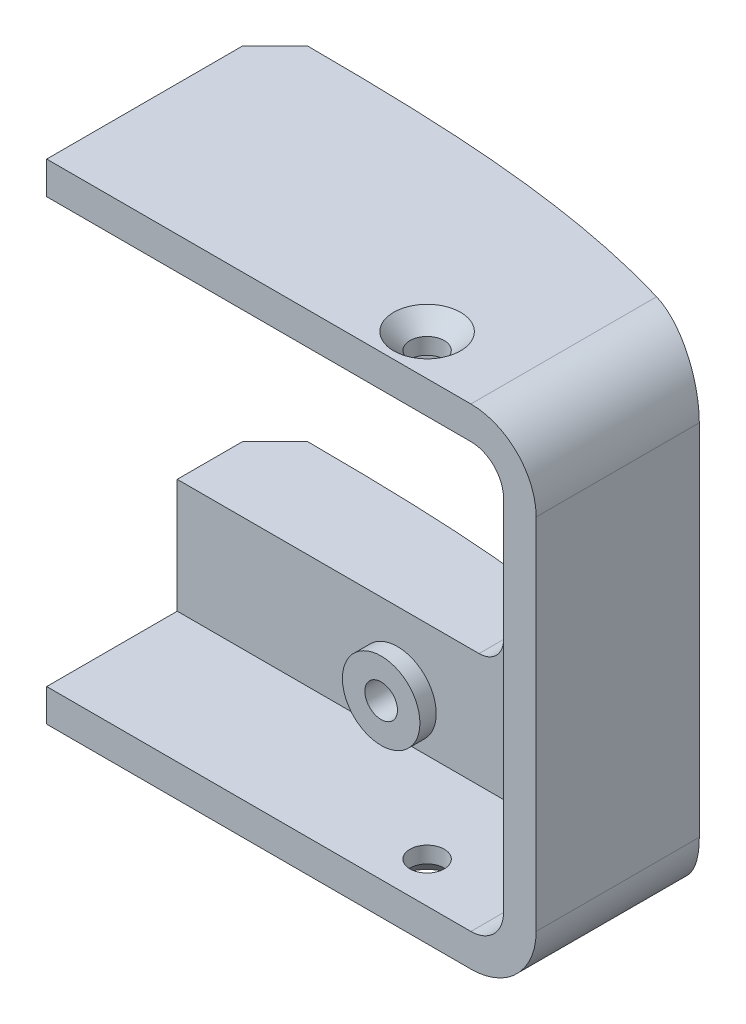
SolidWorks part; units mm, degrees
ref_plane "前视基准面" through (0, 0, 0) normal (0, 0, 1) x (1, 0, 0)
ref_plane "上视基准面" through (0, 0, 0) normal (0, 1, 0) x (1, 0, 0)
ref_plane "右视基准面" through (0, 0, 0) normal (1, 0, 0) x (0, 0, -1)
other "Configuration Table"
sketch "草图2" plane through (0, 0, 0) normal (0, 0, 1) x (1, 0, 0)
  line L1 (18.0576, 5.4113) -> (-11.9424, 5.4113)
  line L2 (18.0576, 5.4113) -> (18.0576, -24.5887)
  line L3 (18.0576, -24.5887) -> (-11.9424, -24.5887)
  line L4 (-11.9424, 5.4113) -> (-11.9424, -24.5887)
  dimension "D1" = 30
  dimension "D2" = 30
extrude "凸台-拉伸1" add sketch "草图2" against normal blind 10
shell "抽壳1" thickness 2 removed face at (-11.9424, -9.5887, -5)
sketch "草图3" plane through (0, 0, 0) normal (0, 0, 1) x (1, 0, 0)
  line L0 (-11.9424, 5.4113) -> (-11.9424, -24.5887) construction
  line L1 (-11.9424, -22.5887) -> (16.0576, -22.5887)
  line L2 (-11.9424, -22.5887) -> (-11.9424, 3.4113)
  line L3 (-11.9424, 3.4113) -> (16.0576, 3.4113)
  line L4 (16.0576, -22.5887) -> (16.0576, 3.4113)
  line L5 (16.0576, -22.5887) -> (16.0576, 3.4113) construction
extrude "切除-拉伸1" cut sketch "草图3" against normal up to next
sketch "草图4" plane through (0, -24.5887, 0) normal (0, -1, 0) x (1, 0, 0)
  line L1 (-11.9424, -10) -> (-11.9424, -14)
  line L2 (-11.9424, -10) -> (18.0576, -10)
  spline S0 degree 3 poles (-11.9424, -14) (-1.4718, -14.0066) (8.4407, -13.8133) (18.0576, -10) knots 0 0 0 0 1 1 1 1
  dimension "D1" = 4
extrude "凸台-拉伸2" add sketch "草图4" against normal up to surface (30 mm away) up to face at (3.0576, 5.4113, -5)
sketch "草图5" plane through (0, 0, 0) normal (0, 0, 1) x (1, 0, 0)
  line L0 (-11.9424, 3.4113) -> (-11.9424, -22.5887) construction
  line L1 (6.5576, -3.5887) -> (-11.9424, -3.5887)
  line L2 (8.0576, -5.0887) -> (8.0576, -14.0887)
  line L3 (6.5576, -15.5887) -> (-11.9424, -15.5887)
  line L4 (-11.9424, -3.5887) -> (-11.9424, -15.5887)
  line L6 (18.0576, -24.5887) -> (18.0576, 5.4113) construction
  arc A1 (8.0576, -14.0887) -> (6.5576, -15.5887) centre (6.5576, -14.0887) cw
  arc A2 (6.5576, -3.5887) -> (8.0576, -5.0887) centre (6.5576, -5.0887) cw
  point P9 (18.0576, -9.5887)
  point P10 (8.0576, -9.5887)
  point P19 (8.0576, -15.5887)
  point P22 (8.0576, -3.5887)
  dimension "D3" = 1.5
  dimension "D1" = 20
  dimension "D2" = 12
extrude "切除-拉伸2" cut sketch "草图5" against normal through all
sketch "草图6" plane through (0, 0, -8) normal (0, 0, 1) x (1, 0, 0)
  circle A0 centre (1.5576, 0.9087) radius 2.375
  circle A1 centre (14.0576, 0.9087) radius 2.375
  circle A2 centre (1.5576, -20.0913) radius 2.375
  circle A3 centre (14.0576, -20.0913) radius 2.375
extrude "凸台-拉伸3" add sketch "草图6" along normal blind 1
sketch "草图7" plane through (0, 0, -7) normal (0, 0, 1) x (1, 0, 0)
  circle A0 centre (1.5576, -20.0913) radius 1
  circle A1 centre (14.0576, -20.0913) radius 1
  circle A2 centre (1.5576, 0.9087) radius 1
  circle A3 centre (14.0576, 0.9087) radius 1
  dimension "D1" = 2
extrude "切除-拉伸3" cut sketch "草图7" against normal blind 3 draft 2
fillet "圆角2" radius 2 2 edges at (16.0576, -22.5887, -4) (16.0576, 3.4113, -4)
fillet "圆角3" radius 4 2 edges at (18.0576, -24.5887, -5) (18.0576, 5.4113, -5)
sketch "草图8" plane through (0, 5.4113, 0) normal (0, 1, 0) x (1, 0, 0)
  circle A0 centre (8.8741, 2.5) radius 1.05
  dimension "D1" = 2.1
extrude "切除-拉伸4" cut sketch "草图8" against normal through all
chamfer "倒角1" distance 1 angle 45 2 edges at (7.8241, -24.5887, -2.5) (7.8241, 5.4113, -2.5)
chamfer "倒角2" distance 2 angle 45 2 edges at (-11.9424, 0.9113, -14) (-11.9424, -20.0887, -14) first distance on face at (1.8442, -9.5131, -12.6965)
